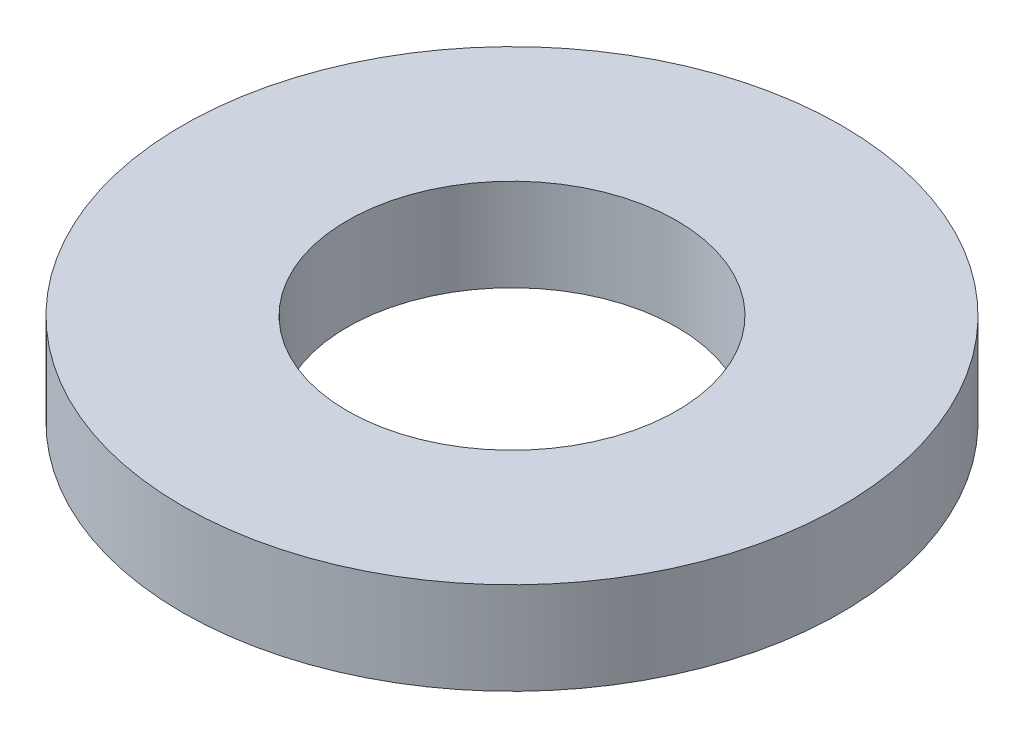
SolidWorks part; units mm, degrees
ref_plane "Front Plane" through (0, 0, 0) normal (0, 0, 1) x (1, 0, 0)
ref_plane "Top Plane" through (0, 0, 0) normal (0, 1, 0) x (1, 0, 0)
ref_plane "Right Plane" through (0, 0, 0) normal (1, 0, 0) x (0, 0, -1)
sketch "Sketch1" plane through (0, 0, 0) normal (0, 1, 0) x (1, 0, 0)
  circle A0 centre (0, 0) radius 100
  dimension "FLANGE_OD" = 200
extrude "Boss-Extrude1" add sketch "Sketch1" along normal blind 28
sketch "Sketch2" plane through (0, 0, 0) normal (0, 1, 0) x (1, 0, 0)
  circle A0 centre (0, 0) radius 50
  dimension "BORE_D" = 100
extrude "Cut-Extrude1" cut sketch "Sketch2" along normal through all
sketch "Sketch3" plane through (0, 28, 0) normal (0, 1, 0) x (1, 0, 0)
  circle A0 centre (0, 0) radius 44.7734 construction
  circle A1 centre (-44.7734, 0) radius 2.6486
  dimension "BOLT_D" = 5.2972
  dimension "BOLT_PCD" = 89.5468
extrude "Cut-Extrude2" cut sketch "Sketch3" against normal blind 27.9909 rebuild error yes
pattern_circular "CirPattern1" count 3 over 360 rebuild error yes
